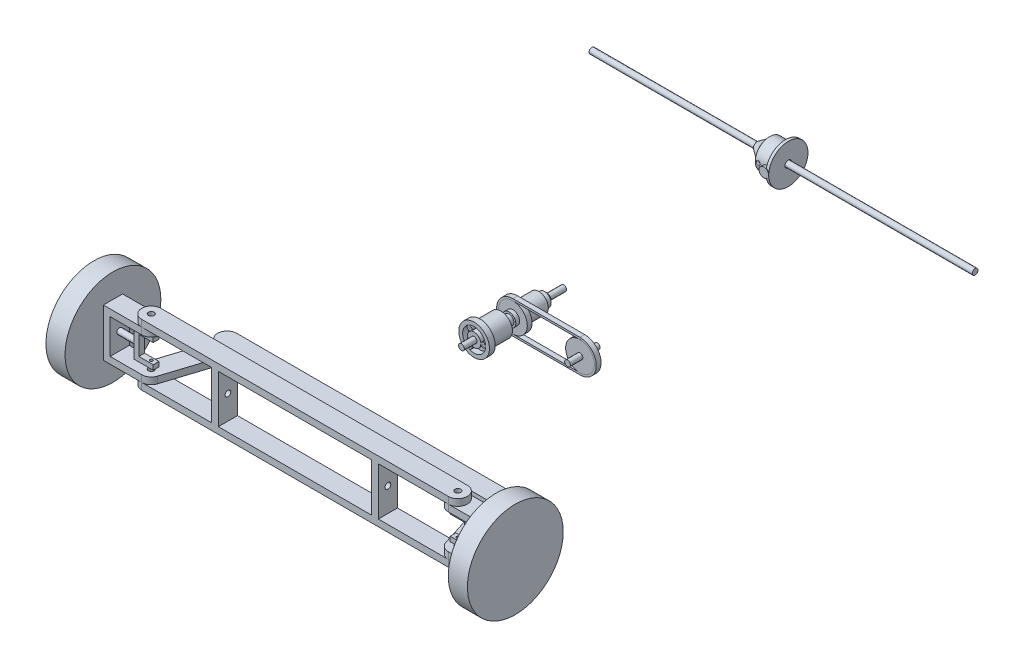
SolidWorks part; units mm, degrees
other "RD Pinion"
other "RD Ring Gear"
other "RD L Gear Right"
other "RD L Gear Left"
other "RD S Gear Outer"
other "RD S Gear Inner"
other "RD S Gear Inner"
other "Tie Plate"
other "Front Right Knuckle"
other "Front Left Knuckle"
other "Front Plate"
other "Main Shaft"
other "Front Right Wheel"
other "Front Left Wheel"
ref_plane "Front Plane" through (0, 0, 0) normal (0, 0, 1) x (1, 0, 0)
ref_plane "Top Plane" through (0, 0, 0) normal (0, 1, 0) x (1, 0, 0)
ref_plane "Right Plane" through (0, 0, 0) normal (1, 0, 0) x (0, 0, -1)
sketch "Top View Layout" plane through (0, 0, 0) normal (0, 1, 0) x (1, 0, 0)
  line L0 (-100, 125) -> (100, 125)
  line L1 (0, 125) -> (0, -125)
  line L2 (-100, -125) -> (100, -125)
  line L3 (0, -15) -> (35, -15) construction
  line L4 (35, -15) -> (35, -125) construction
  line L5 (2.5, 114.75) -> (2.5, 135.25) construction
  line L6 (-2.5, 114.75) -> (2.5, 114.75) construction
  line L7 (-8.75, 127) -> (-2.75, 127) construction
  line L8 (-2.5, 114.75) -> (2.5, 114.75) construction
  line L9 (-2.5, 114.75) -> (-2.5, 116.25) construction
  line L10 (-2.5, 116.25) -> (2.5, 116.25) construction
  line L11 (2.5, 114.75) -> (2.5, 116.25) construction
  line L12 (2.5, 135.25) -> (1, 135.25) construction
  line L13 (2.5, 135.25) -> (2.5, 114.75) construction
  line L14 (2.5, 114.75) -> (1, 114.75) construction
  line L15 (1, 135.25) -> (1, 114.75) construction
  line L16 (-4.25, 128.5) -> (-2.75, 128.5) construction
  line L17 (-4.25, 128.5) -> (-4.25, 121.5) construction
  line L18 (-4.25, 121.5) -> (-2.75, 121.5) construction
  line L19 (-2.75, 128.5) -> (-2.75, 121.5) construction
  line L20 (-4.25, 128.5) -> (-2.75, 121.5) construction
  line L21 (-4.25, 121.5) -> (-2.75, 128.5) construction
  line L22 (-8.75, 128.5) -> (-7.25, 128.5) construction
  line L23 (-8.75, 128.5) -> (-8.75, 121.5) construction
  line L24 (-8.75, 121.5) -> (-7.25, 121.5) construction
  line L25 (-7.25, 128.5) -> (-7.25, 121.5) construction
  line L26 (-8.75, 128.5) -> (-7.25, 121.5) construction
  line L27 (-8.75, 121.5) -> (-7.25, 128.5) construction
  line L28 (-8.75, 123) -> (-2.75, 123) construction
  line L29 (-5.75, 123) -> (-5.75, 120.2863) construction
  line L30 (-5.75, 127) -> (-5.75, 129.2691) construction
  point P8 (0, 114.75)
  point P9 (0, 0)
  point P11 (2.5, 125)
  point P16 (2.5, 125)
  point P19 (0, 114.75)
  point P23 (-3.5, 125)
  point P28 (-8, 125)
  dimension "D1" = 250
  dimension "D2" = 200
  dimension "D3" = 35
  dimension "D4" = 15
  dimension "D5" = 5
  dimension "D6" = 20.5
  dimension "D7" = 1.5
  dimension "D8" = 1.5
  dimension "D9" = 1.5
  dimension "D10" = 7
  dimension "D11" = 3.5
  dimension "D12" = 8
  dimension "D13" = 1.5
  dimension "D14" = 1.5
ref_plane "Left" through (100, 0, 0) normal (-1, 0, 0) x (0, 0, 1)
ref_plane "Right" through (-100, 0, 0) normal (-1, 0, 0) x (0, 0, 1)
sketch "Left Wheels" plane through (100, 0, 0) normal (-1, 0, 0) x (0, 0, 1)
  circle A0 centre (125, 0) radius 25
  circle A1 centre (-125, 0) radius 25
  dimension "D1" = 50
  dimension "D2" = 50
sketch "Right Wheels" plane through (-100, 0, 0) normal (-1, 0, 0) x (0, 0, 1)
  circle A0 centre (-125, 0) radius 25 construction
  circle A1 centre (125, 0) radius 25 construction
  circle A2 centre (-125, 0) radius 25
  circle A3 centre (125, 0) radius 25
ref_plane "Rear Differential Pinion Plane" through (0, 0, -114.75) normal (0, 0, 1) x (1, 0, 0)
sketch "Rear Differential Pinion Profile" plane through (0, 0, -114.75) normal (0, 0, 1) x (1, 0, 0)
  circle A0 centre (0, 0) radius 2.5
ref_plane "Rear Differential Ring Gear Plane" through (2.5, 0, 0) normal (1, 0, 0) x (0, 0, -1)
ref_plane "Rear Axle" through (0, 0, -125) normal (0, 0, 1) x (1, 0, 0)
sketch "Rear Differential Ring Gear Profile" plane through (2.5, 0, 0) normal (1, 0, 0) x (0, 0, -1)
  line L0 (114.75, 0) -> (135.25, 0) construction
  circle A0 centre (125, 0) radius 10.25
extrude "Rear Differential Pinion" add sketch "Rear Differential Pinion Profile" against normal blind 1.5 contours A0
extrude "Rear Differential Ring Gear" add sketch "Rear Differential Ring Gear Profile" against normal blind 1.5 separate body contours A0
ref_plane "RD Inner L Gear Plane" through (-2.75, 0, 0) normal (1, 0, 0) x (0, 0, -1)
ref_plane "RD Outer L Gear Plane" through (-8.75, 0, 0) normal (1, 0, 0) x (0, 0, -1)
sketch "RD Inner L Gear Profile" plane through (-2.75, 0, 0) normal (1, 0, 0) x (0, 0, -1)
  circle A0 centre (125, 0) radius 3.5
sketch "RD Outer L Gear Profile" plane through (-8.75, 0, 0) normal (1, 0, 0) x (0, 0, -1)
  line L0 (128.5, 0) -> (121.5, 0) construction
  circle A0 centre (125, 0) radius 3.5
ref_plane "RD Inner S Gear Plane" through (0, 0, -121.5) normal (0, 0, 1) x (1, 0, 0)
ref_plane "RD Outer S Gear Plane" through (0, 0, -128.5) normal (0, 0, 1) x (1, 0, 0)
sketch "RD Inner S Gear Profile" plane through (0, 0, -121.5) normal (0, 0, 1) x (1, 0, 0)
  line L0 (-8.75, 0) -> (-7.25, 0) construction
  circle A0 centre (-5.75, 0) radius 3
sketch "RD Outer S Gear Profile" plane through (0, 0, -128.5) normal (0, 0, 1) x (1, 0, 0)
  line L0 (-8.75, 0) -> (-7.25, 0) construction
  circle A2 centre (-5.75, 0) radius 3
extrude "RD Outer L Gear Extrude" add sketch "RD Outer L Gear Profile" along normal blind 1.5 separate body contours A0
extrude "RD Inner L Gear Extrude" add sketch "RD Inner L Gear Profile" against normal blind 1.5 separate body contours A0
extrude "RD Outer S Gear Extrude" add sketch "RD Outer S Gear Profile" along normal blind 1.5 separate body contours A2
extrude "RD Inner S Gear Extrude" add sketch "RD Inner S Gear Profile" against normal blind 1.5 separate body contours A0
sketch "RD Ring Gear Case Profile" plane through (1, 0, 0) normal (-1, 0, 0) x (0, 0, 1)
  line L0 (-121.5, 3.2113) -> (-121.5, -3.2113)
  line L1 (-128.5, 3.2113) -> (-128.5, -3.2113)
  line L2 (-121.5, 6.6332) -> (-121.5, 3.2113) construction
  line L3 (-128.5, 6.6332) -> (-128.5, 3.2113) construction
  line L4 (-121.5, -3.2113) -> (-121.5, -6.6332) construction
  line L5 (-128.5, -3.2113) -> (-128.5, -6.6332) construction
  circle A0 centre (-125, 0) radius 7.5
  arc A1 (-121.5, 3.2113) -> (-128.5, 3.2113) centre (-125, 0) ccw
  arc A2 (-121.5, -3.2113) -> (-121.5, 3.2113) centre (-125, 0) ccw construction
  arc A3 (-128.5, 3.2113) -> (-128.5, -3.2113) centre (-125, 0) ccw construction
  arc A4 (-128.5, -3.2113) -> (-121.5, -3.2113) centre (-125, 0) ccw
  point P7 (-121.5, 0)
  dimension "D1" = 15
  dimension "D2" = 9.5
extrude "RD Ring Gear Case " add sketch "RD Ring Gear Case Profile" along normal blind 8.25
sketch "Sketch11" plane through (-7.25, 0, 0) normal (-1, 0, 0) x (0, 0, 1)
  circle A0 centre (-125, 0) radius 5.5
  circle A1 centre (-125, 0) radius 4.75
  arc A2 (-121.5, 3.2113) -> (-128.5, 3.2113) centre (-125, 0) ccw construction
  dimension "D1" = 11
extrude "Boss-Extrude8" add sketch "Sketch11" along normal up to vertex up to point (-8.75, 0, -128.5)
fillet "Fillet1" radius 2 1 edges at (-7.25, 0, -119.5)
sketch "Sketch12" plane through (0, 0, -125) normal (0, 0, 1) x (1, 0, 0)
  line L0 (-8.75, 0) -> (-13.75, 0) construction
  line L1 (-8.75, 0) -> (-7.25, 0) construction
  line L2 (-8.75, 0) -> (-7.25, 0) construction
  line L3 (-100, 0) -> (100, 0) construction
  line L4 (-100, 0) -> (100, 0) construction
  line L5 (-8.75, 5.5) -> (-8.75, -5.5) construction
  line L6 (-13.75, 0) -> (-13.75, 2)
  line L7 (-13.75, 2) -> (-8.75, 5.5)
  line L8 (-13.75, 0) -> (-8.75, 0)
  line L9 (-8.75, 0) -> (-8.75, 5.5)
  point P15 (-13.75, 1)
  dimension "D1" = 5
  dimension "D2" = 2
revolve "Revolve1" add sketch "Sketch12" angle 360 about L0
sketch "Sketch13" plane through (2.5, 0, 0) normal (1, 0, 0) x (0, 0, -1)
  circle A0 centre (125, 0) radius 1.75
  dimension "D1" = 3.5
extrude "Cut-Extrude1" cut sketch "Sketch13" against normal through all
sketch "Sketch14" plane through (0, 0, -121.5) normal (0, 0, 1) x (1, 0, 0)
  circle A0 centre (-5.75, 0) radius 1
  dimension "D1" = 2
extrude "Boss-Extrude9" add sketch "Sketch14" along normal blind 4
sketch "Sketch15" plane through (0, 0, -121.5) normal (0, 0, 1) x (1, 0, 0)
  circle A0 centre (-5.75, 0) radius 1.1
  dimension "D1" = 2.2
extrude "Cut-Extrude2" cut sketch "Sketch15" against normal through all both and the other way through all
extrude "Boss-Extrude10" add sketch "Sketch14<2>" against normal blind 4 from surface starting at face at (-2.75, 0, -128.5)
sketch "Sketch14<2>" plane through (0, 0, -121.5) normal (0, 0, 1) x (1, 0, 0) same geometry as "Sketch14"
sketch "Sketch16" plane through (-8.75, 0, 0) normal (-1, 0, 0) x (0, 0, 1)
  circle A0 centre (-125, 0) radius 1.5
  dimension "D1" = 3
extrude "Boss-Extrude11" add sketch "Sketch16" along normal up to vertex (91.25 mm away) up to point (-100, 0, -125)
sketch "Sketch17" plane through (-2.75, 0, 0) normal (1, 0, 0) x (0, 0, -1)
  circle A0 centre (125, 0) radius 1.5 construction
  circle A1 centre (125, 0) radius 1.5
extrude "Boss-Extrude12" add sketch "Sketch17" along normal up to vertex (102.75 mm away) up to point (100, 0, -125)
sketch "Transfer Case Layout" plane through (0, 0, 0) normal (0, 1, 0) x (1, 0, 0)
  line L0 (0, 125) -> (0, -125) construction
  line L1 (-7.5, -13.75) -> (7.5, -13.75)
  line L2 (-7.5, -13.75) -> (-7.5, -16.25)
  line L3 (-7.5, -16.25) -> (7.5, -16.25)
  line L4 (7.5, -13.75) -> (7.5, -16.25)
  line L5 (-7.5, -13.75) -> (7.5, -16.25) construction
  line L6 (-7.5, -16.25) -> (7.5, -13.75) construction
  line L7 (27.5, -13.75) -> (42.5, -13.75)
  line L8 (27.5, -13.75) -> (27.5, -16.25)
  line L9 (27.5, -16.25) -> (42.5, -16.25)
  line L10 (42.5, -13.75) -> (42.5, -16.25)
  line L11 (27.5, -13.75) -> (42.5, -16.25) construction
  line L12 (27.5, -16.25) -> (42.5, -13.75) construction
  line L13 (2.5, -17.25) -> (-2.5, -17.25)
  line L14 (2.5, -17.25) -> (2.5, -16.25)
  line L15 (2.5, -16.25) -> (-2.5, -16.25)
  line L16 (-2.5, -17.25) -> (-2.5, -16.25)
  line L17 (2.5, -17.25) -> (-2.5, -16.25) construction
  line L18 (2.5, -16.25) -> (-2.5, -17.25) construction
  line L19 (-2, -4.75) -> (-2, -10.75)
  line L20 (3.5, -18.25) -> (-3.5, -18.25)
  line L21 (3.5, -18.25) -> (3.5, -16.25)
  line L22 (3.5, -16.25) -> (-3.5, -16.25)
  line L23 (-3.5, -18.25) -> (-3.5, -16.25)
  line L24 (3.5, -18.25) -> (-3.5, -16.25) construction
  line L25 (3.5, -16.25) -> (-3.5, -18.25) construction
  line L26 (2.5, -20) -> (-2.5, -20)
  line L27 (2.5, -20) -> (2.5, -17.5)
  line L28 (2.5, -17.5) -> (-2.5, -17.5)
  line L29 (-2.5, -20) -> (-2.5, -17.5)
  line L30 (2.5, -20) -> (-2.5, -17.5) construction
  line L31 (2.5, -17.5) -> (-2.5, -20) construction
  line L32 (-3.5, -9.25) -> (3.5, -9.25)
  line L33 (-3.5, -9.25) -> (-3.5, -10.75)
  line L34 (-3.5, -10.75) -> (3.5, -10.75)
  line L35 (3.5, -9.25) -> (3.5, -10.75)
  line L36 (-3.5, -9.25) -> (3.5, -10.75) construction
  line L37 (-3.5, -10.75) -> (3.5, -9.25) construction
  line L38 (-3.5, -4.75) -> (3.5, -4.75)
  line L39 (-3.5, -4.75) -> (-3.5, -6.25)
  line L40 (-3.5, -6.25) -> (3.5, -6.25)
  line L41 (3.5, -4.75) -> (3.5, -6.25)
  line L42 (-3.5, -4.75) -> (3.5, -6.25) construction
  line L43 (-3.5, -6.25) -> (3.5, -4.75) construction
  line L44 (2, -4.75) -> (2, -10.75)
  line L45 (0, -6.25) -> (0, -9.25) construction
  line L46 (-5, -2.75) -> (5, -2.75) construction
  line L47 (-5, -2.75) -> (-5, -12.75) construction
  line L48 (-5, -12.75) -> (5, -12.75) construction
  line L49 (5, -2.75) -> (5, -12.75) construction
  line L50 (-5, -2.75) -> (5, -12.75) construction
  line L51 (-5, -12.75) -> (5, -2.75) construction
  line L52 (-6, -22.5) -> (-6, -24)
  line L53 (-2.5, -1.75) -> (2.5, -1.75)
  line L54 (-2.5, -1.75) -> (-2.5, -2.75)
  line L55 (-2.5, -2.75) -> (2.5, -2.75)
  line L56 (2.5, -1.75) -> (2.5, -2.75)
  line L57 (-2.5, -1.75) -> (2.5, -2.75) construction
  line L58 (-2.5, -2.75) -> (2.5, -1.75) construction
  line L59 (-2.5, 1.25) -> (2.5, 1.25)
  line L60 (-2.5, 1.25) -> (-2.5, -0.75)
  line L61 (-2.5, -0.75) -> (2.5, -0.75)
  line L62 (2.5, 1.25) -> (2.5, -0.75)
  line L63 (-2.5, 1.25) -> (2.5, -0.75) construction
  line L64 (-2.5, -0.75) -> (2.5, 1.25) construction
  line L65 (3.5, 0.25) -> (-3.5, 0.25)
  line L66 (3.5, 0.25) -> (3.5, -2.25)
  line L67 (3.5, -2.25) -> (-3.5, -2.25)
  line L68 (-3.5, 0.25) -> (-3.5, -2.25)
  line L69 (3.5, 0.25) -> (-3.5, -2.25) construction
  line L70 (3.5, -2.25) -> (-3.5, 0.25) construction
  line L71 (-2.5, -22.5) -> (2.5, -22.5)
  line L72 (-2.5, -22.5) -> (-2.5, -27.5)
  line L73 (-2.5, -27.5) -> (2.5, -27.5)
  line L74 (2.5, -22.5) -> (2.5, -27.5)
  line L75 (-2.5, -22.5) -> (2.5, -27.5) construction
  line L76 (-2.5, -27.5) -> (2.5, -22.5) construction
  line L77 (-6, -24) -> (6, -24)
  line L78 (6, -24) -> (6, -22.5)
  line L79 (6, -22.5) -> (-6, -22.5)
  line L80 (-4.5, -22.5) -> (-4.5, -24)
  line L81 (4.5, -22.5) -> (4.5, -24)
  line L82 (-6, -24) -> (-6, -33.5) construction
  line L83 (2.5, -29.5) -> (-2.5, -29.5)
  line L84 (2.5, -29.5) -> (2.5, -28)
  line L85 (2.5, -28) -> (-2.5, -28)
  line L86 (-2.5, -29.5) -> (-2.5, -28)
  line L87 (2.5, -29.5) -> (-2.5, -28) construction
  line L88 (2.5, -28) -> (-2.5, -29.5) construction
  line L89 (-4.5, -26.5) -> (4.5, -26.5)
  line L90 (-4.5, -26.5) -> (-4.5, -29.5)
  line L91 (-4.5, -29.5) -> (4.5, -29.5)
  line L92 (4.5, -26.5) -> (4.5, -29.5)
  line L93 (-4.5, -26.5) -> (4.5, -29.5) construction
  line L94 (-4.5, -29.5) -> (4.5, -26.5) construction
  line L95 (6, -24) -> (6, -33.5) construction
  line L96 (-3.5, -33.5) -> (-3.5, -36.5)
  line L97 (6, -36.5) -> (-6, -36.5)
  line L98 (6, -36.5) -> (6, -33.5)
  line L99 (6, -33.5) -> (-6, -33.5)
  line L100 (-6, -36.5) -> (-6, -33.5)
  line L101 (6, -36.5) -> (-6, -33.5) construction
  line L102 (6, -33.5) -> (-6, -36.5) construction
  line L103 (3.5, -33.5) -> (3.5, -36.5)
  line L104 (0, -28) -> (0, -43.1129)
  line L109 (8, -36.5) -> (-8, -36.5)
  line L110 (8, -36.5) -> (8, -33.5)
  line L111 (8, -33.5) -> (-8, -33.5)
  line L112 (-8, -36.5) -> (-8, -33.5)
  line L113 (8, -36.5) -> (-8, -33.5) construction
  line L114 (8, -33.5) -> (-8, -36.5) construction
  line L115 (0, -27.5) -> (0, -9.25)
  line L116 (0, -6.25) -> (0, -1.75)
  line L117 (0, -0.75) -> (0, 11.0375)
  line L118 (35, -22.7597) -> (35, -7.2403)
  point P0 (0, -15)
  point P6 (35, -15)
  point P12 (0, -16.75)
  point P19 (0, -17.25)
  point P24 (0, -18.75)
  point P29 (0, -10)
  point P34 (0, -5.5)
  point P43 (0, -7.75)
  point P50 (0, -2.25)
  point P55 (0, 0.25)
  point P60 (0, -1)
  point P65 (0, -25)
  point P72 (0, -22.5)
  point P79 (0, -28.75)
  point P84 (0, -28)
  point P92 (0, -35)
  point P98 (0, -35)
  point P99 (0, -35)
  point P113 (35, -15)
  dimension "D1" = 2.5
  dimension "D2" = 2.5
  dimension "D3" = 15
  dimension "D4" = 15
  dimension "D5" = 1
  dimension "D6" = 5
  dimension "D7" = 7
  dimension "D8" = 2
  dimension "D9" = 0.25
  dimension "D10" = 2.5
  dimension "D11" = 7
  dimension "D12" = 5
  dimension "D13" = 1.5
  dimension "D14" = 1.5
  dimension "D15" = 1.5
  dimension "D16" = 1.5
  dimension "D17" = 6
  dimension "D18" = 2
  dimension "D19" = 1.5
  dimension "D20" = 5
  dimension "D21" = 1
  dimension "D22" = 2
  dimension "D23" = 1
  dimension "D24" = 7
  dimension "D25" = 2.5
  dimension "D26" = 0.5
  dimension "D27" = 5
  dimension "D28" = 5
  dimension "D29" = 10
  dimension "D30" = 1.5
  dimension "D31" = 12
  dimension "D32" = 1.5
  dimension "D33" = 1.5
  dimension "D34" = 1.5
  dimension "D35" = 0.5
  dimension "D36" = 3
  dimension "D37" = 3
  dimension "D38" = 20
  dimension "D39" = 2.5
  dimension "D40" = 2.5
  dimension "D41" = 7
  dimension "D42" = 2
  dimension "D43" = 16
ref_plane "FWD Sprocket Plane" through (0, 0, 15) normal (0, 0, 1) x (1, 0, 0)
sketch "Sketch19" plane through (0, 0, 15) normal (0, 0, 1) x (1, 0, 0)
  circle A0 centre (35, 0) radius 7.5
  circle A1 centre (0, 0) radius 7.5
  point P6 (7.5, 0)
  point P9 (27.5, 0)
extrude "FWD Sprockets" add sketch "Sketch19" along normal up to vertex (1.25 mm away) and the other way up to vertex (1.25 mm away) separate body up to point (-7.5, 0, 16.25) other way up to point (-7.5, 0, 13.75)
sketch "Sketch20" plane through (0, 0, 15) normal (0, 0, 1) x (1, 0, 0)
  line L0 (0, 8.5) -> (35, 8.5)
  line L1 (0, -8.5) -> (35, -8.5)
  line L2 (0, 7.5) -> (35, 7.5)
  line L3 (0, -7.5) -> (35, -7.5)
  circle A0 centre (0, 0) radius 7.5 construction
  arc A1 (0, 7.5) -> (0, -7.5) centre (0, 0) ccw
  circle A2 centre (35, 0) radius 7.5 construction
  arc A3 (35, -7.5) -> (35, 7.5) centre (35, 0) ccw
  arc A4 (0, 8.5) -> (0, -8.5) centre (0, 0) ccw
  arc A5 (35, -8.5) -> (35, 8.5) centre (35, 0) ccw
  arc A6 (4, -7.5) -> (4, 7.5) centre (0, 0) ccw construction
  arc A7 (0, -7.5) -> (0, 7.5) centre (0, 0) ccw construction
  arc A8 (35, 7.5) -> (35, -7.5) centre (35, 0) ccw construction
  arc A9 (31, 7.5) -> (31, -7.5) centre (35, 0) ccw construction
  arc A10 (4, 7.5) -> (0, 8.5) centre (0, 0) ccw construction
  arc A11 (35, 8.5) -> (31, 7.5) centre (35, 0) ccw construction
  arc A12 (31, -7.5) -> (35, -8.5) centre (35, 0) ccw construction
  arc A13 (0, -8.5) -> (4, -7.5) centre (0, 0) ccw construction
  dimension "D1" = 1
  dimension "D2" = 1
extrude "FWD Sprocket Chain" add sketch "Sketch20" along normal up to surface and the other way up to surface separate body up to face at (7.5, 0, 16.25) other way up to face at (7.5, 0, 13.75)
sketch "Sketch21" plane through (0, 0, 16.25) normal (0, 0, 1) x (1, 0, 0)
  circle A0 centre (0, 0) radius 2.5
  point P3 (2.5, 0)
extrude "FWD Sprocket Dog Gear" add sketch "Sketch21" along normal up to vertex (1 mm away) up to point (-2.5, 0, 17.25)
ref_plane "Mode Sleeve Gear Plane" through (0, 0, 18.25) normal (0, 0, 1) x (1, 0, 0)
sketch "Sketch22" plane through (0, 0, 18.25) normal (0, 0, 1) x (1, 0, 0)
  circle A0 centre (0, 0) radius 3.5
  circle A1 centre (0, 0) radius 2.5 construction
  circle A2 centre (0, 0) radius 2.5
extrude "Mode Sleeve Gear" add sketch "Sketch22" against normal up to vertex (2 mm away) separate body up to point (3.5, 0, 16.25)
sketch "Sketch23" plane through (0, 0, 18.25) normal (0, 0, 1) x (1, 0, 0)
  circle A0 centre (0, 0) radius 2.5 construction
  circle A1 centre (0, 0) radius 2.5
extrude "Mode Sleeve Main Shaft Gear" add sketch "Sketch23" along normal up to vertex (1.75 mm away) and the other way up to vertex (0.75 mm away) separate body up to point (2.5, 0, 20) other way up to point (2.5, 0, 17.5)
ref_plane "Range Sleeve Rear Plane" through (0, 0, 22.5) normal (0, 0, 1) x (1, 0, 0)
sketch "Sketch24" plane through (0, 0, 22.5) normal (0, 0, 1) x (1, 0, 0)
  circle A0 centre (0, 0) radius 2.5
extrude "Main Shaft Range Sleeve Gear" add sketch "Sketch24" along normal up to vertex (5 mm away) separate body up to point (-2.5, 0, 27.5)
sketch "Sketch25" plane through (0, 0, 22.5) normal (0, 0, 1) x (1, 0, 0)
  circle A0 centre (0, 0) radius 6
  circle A3 centre (0, 0) radius 4.5
extrude "Carrier Range Sleeve Gear" add sketch "Sketch25" along normal up to vertex (1.5 mm away) separate body up to point (6, 0, 24)
ref_plane "Range Sleeve Input Shaft Side" through (0, 0, 29.5) normal (0, 0, 1) x (1, 0, 0)
sketch "Sketch27" plane through (0, 0, 29.5) normal (0, 0, 1) x (1, 0, 0)
  circle A0 centre (0, 0) radius 2.5
extrude "Input Range Sleeve Gear" add sketch "Sketch27" against normal up to vertex (1.5 mm away) separate body up to point (2.5, 0, 28)
sketch "Sketch28" plane through (0, 0, 29.5) normal (0, 0, 1) x (1, 0, 0)
  circle A0 centre (0, 0) radius 4.5
  circle A1 centre (0, 0) radius 2.5 construction
  circle A2 centre (0, 0) radius 2.5
extrude "Range Sleeve Sleeve Gear" add sketch "Sketch28" against normal up to vertex (3 mm away) separate body up to point (4.5, 0, 26.5)
ref_plane "Planetary Input Side Plane" through (0, 0, 36.5) normal (0, 0, 1) x (1, 0, 0)
sketch "Sketch29" plane through (0, 0, 36.5) normal (0, 0, 1) x (1, 0, 0)
  circle A0 centre (0, 0) radius 3.5
extrude "Planetary Sun Gear" add sketch "Sketch29" against normal up to vertex (3 mm away) separate body up to point (3.5, 0, 33.5)
sketch "Sketch30" plane through (0, 0, 36.5) normal (0, 0, 1) x (1, 0, 0)
  line L0 (6, 0) -> (-6, 0) construction
  circle A0 centre (4.75, 0) radius 1.25
extrude "Planetary Planet Gear" add sketch "Sketch30" against normal up to vertex (3 mm away) separate body up to point (6, 0, 33.5)
pattern_circular "Planetary Planet Gear x 3" count 3 over 360 about axis through (0, 0, 28) along (0, 0, 1) reverse direction yes of bodies 132
sketch "Sketch31" plane through (0, 0, 36.5) normal (0, 0, 1) x (1, 0, 0)
  circle A0 centre (0, 0) radius 6
  circle A1 centre (0, 0) radius 8
extrude "Planetary Ring Gear" add sketch "Sketch31" against normal up to vertex (3 mm away) separate body up to point (8, 0, 33.5)
ref_plane "Planetary Rear Side Plane" through (0, 0, 33.5) normal (0, 0, 1) x (1, 0, 0)
sketch "Sketch32" plane through (0, 0, 33.5) normal (0, 0, 1) x (1, 0, 0)
  line L0 (3.5, 0) -> (6, 0) construction
  line L1 (0, 0) -> (4.75, 0) construction
  line L2 (0, 0) -> (-2.375, -4.1136) construction
  circle A0 centre (0, 0) radius 6
  circle A1 centre (4.75, 0) radius 0.5
  circle A2 centre (-2.375, -4.1136) radius 0.5
  circle A3 centre (-2.375, 4.1136) radius 0.5
  point P4 (4.75, 0)
  dimension "D1" = 1
  dimension "D3" = 120
  dimension "D4" = 4.75
  dimension "D2" = 3
extrude "Carrier" add sketch "Sketch32" against normal blind 1 separate body contours A3 | A0 A3 A2 A1 | A1 | A2 region at (0, 0, 33.5) region at (4.75, 0, 33.5) region at (-2.375, -4.1136, 33.5) region at (-2.375, 4.1136, 33.5)
extrude "Carrier Shafts" add sketch "Sketch32<3>" along normal up to vertex (3 mm away) contours A1 | A2 | A3 region at (4.75, 0, 33.5) region at (-2.375, -4.1136, 33.5) up to point (-3.5, 0, 36.5)
sketch "Sketch32<3>" plane through (0, 0, 33.5) normal (0, 0, 1) x (1, 0, 0) same geometry as "Sketch32"
sketch "Sketch33" plane through (0, 0, 33.5) normal (0, 0, 1) x (1, 0, 0)
  circle A0 centre (0, 0) radius 6 construction
  circle A1 centre (0, 0) radius 6
  circle A2 centre (0, 0) radius 5.5
  dimension "D1" = 0.5
extrude "Carrier Range Sleeve Gear Connect" add sketch "Sketch33" against normal up to surface (9.5 mm away) up to face at (6, 0, 24)
ref_plane "Center Diff Main Shaft Sidegear Plane" through (0, 0, 10.75) normal (0, 0, 1) x (1, 0, 0)
sketch "Sketch34" plane through (0, 0, 10.75) normal (0, 0, 1) x (1, 0, 0)
  circle A0 centre (0, 0) radius 3.5
extrude "Center Diff Main Shaft Side Gear" add sketch "Sketch34" against normal up to vertex (1.5 mm away) separate body up to point (3.5, 0, 9.25)
ref_plane "Center Diff Rear Shaft Sidegear Plane" through (0, 0, 4.75) normal (0, 0, 1) x (1, 0, 0)
ref_plane "Center Diff Mid Plane" through (0, 0, 7.75) normal (0, 0, 1) x (1, 0, 0)
mirror "Center Diff Rear Shaft Side Gear" about plane through (0, 0, 7.75) normal (0, 0, 1) of bodies 139
ref_plane "Center Diff Right Pinion Inner Plane" through (-2, 0, 0) normal (-1, 0, 0) x (0, 0, 1)
sketch "Sketch35" plane through (-2, 0, 0) normal (-1, 0, 0) x (0, 0, 1)
  line L0 (4.75, 0) -> (10.75, 0) construction
  circle A0 centre (7.75, 0) radius 3
extrude "Center Diff Right Pinion" add sketch "Sketch35" along normal up to vertex (1.5 mm away) separate body up to point (-3.5, 0, 10.75)
ref_plane "Center Diff Left Side Pinion Inner Plane" through (2, 0, 0) normal (-1, 0, 0) x (0, 0, 1)
sketch "Sketch36" plane through (2, 0, 0) normal (-1, 0, 0) x (0, 0, 1)
  line L0 (4.75, 0) -> (10.75, 0) construction
  circle A0 centre (7.75, 0) radius 3
extrude "Center Diff Left Pinion" add sketch "Sketch36" against normal up to vertex (1.5 mm away) separate body up to point (3.5, 0, 4.75)
ref_plane "Center Diff Rear Shaft Side Plane" through (0, 0, 2.75) normal (0, 0, 1) x (1, 0, 0)
sketch "Sketch37" plane through (0, 0, 2.75) normal (0, 0, 1) x (1, 0, 0)
  circle A0 centre (0, 0) radius 5
extrude "Center Diff Rear Axle Side Plate" add sketch "Sketch37" along normal up to vertex (2 mm away) separate body up to point (3.5, 0, 4.75)
mirror "Center Diff Main Shaft Side Plate" about plane through (0, 0, 7.75) normal (0, 0, 1) of bodies 143
sketch "Sketch38" plane through (0, 0, 2.75) normal (0, 0, 1) x (1, 0, 0)
  line L0 (3.5, -2.8284) -> (3.5, 2.8284)
  line L1 (-3.4263, -2.9173) -> (-3.5, -2.8284)
  line L2 (-3.5, -2.8284) -> (-3.5, 2.8284)
  circle A0 centre (0, 0) radius 5 construction
  circle A1 centre (0, 0) radius 5
  arc A2 (3.5, 2.8284) -> (-3.5, 2.8284) centre (0, 0) ccw
  arc A3 (3.5, -2.8284) -> (3.5, 2.8284) centre (0, 0) ccw construction
  arc A4 (-3.5, 2.8284) -> (-3.5, -2.8284) centre (0, 0) ccw construction
  arc A5 (-3.5, -2.8284) -> (3.5, -2.8284) centre (0, 0) ccw
  dimension "D1" = 0.5
extrude "Center Diff Case" add sketch "Sketch38" along normal up to surface (8 mm away) contours A1 A5 L2 A2 L0 region at (-4.8586, 0, 2.75) up to face at (5, 0, 10.75)
sketch "Sketch39" plane through (0, 0, 2.75) normal (0, 0, 1) x (1, 0, 0)
  circle A0 centre (0, 0) radius 2.5
extrude "Center Diff Lock Gear" add sketch "Sketch39" against normal up to vertex (1 mm away) up to point (2.5, 0, 1.75)
ref_plane "Lock Sleeve Plane" through (0, 0, -0.25) normal (0, 0, 1) x (1, 0, 0)
sketch "Sketch41" plane through (0, 0, -0.25) normal (0, 0, 1) x (1, 0, 0)
  circle A0 centre (0, 0) radius 3.5
  circle A1 centre (0, 0) radius 2.5 construction
  circle A2 centre (0, 0) radius 2.5
extrude "Lock Sleeve" add sketch "Sketch41" along normal up to vertex (2.5 mm away) separate body up to point (-3.5, 0, 2.25)
sketch "Sketch42" plane through (0, 0, -0.25) normal (0, 0, 1) x (1, 0, 0)
  circle A0 centre (0, 0) radius 2.5 construction
  circle A1 centre (0, 0) radius 2.5
extrude "Lock Sleeve Rear Shaft Gear" add sketch "Sketch42" along normal up to vertex (1 mm away) and the other way up to vertex (1 mm away) separate body up to point (2.5, 0, 0.75) other way up to point (2.5, 0, -1.25)
sketch "Sketch43" plane through (-2, 0, 0) normal (-1, 0, 0) x (0, 0, 1)
  line L0 (4.75, 0) -> (10.75, 0) construction
  circle A0 centre (7.75, 0) radius 0.5
  dimension "D1" = 1
extrude "Center Diff Pinion Rotation Point Cut" cut sketch "Sketch43" against normal through all both and the other way through all
sketch "Sketch45" plane through (0, 0, 2.75) normal (0, 0, 1) x (1, 0, 0)
  circle A0 centre (0, 0) radius 0.5
  dimension "D1" = 1
extrude "Center Diff Side Gear Rotation Point" cut sketch "Sketch45" against normal through all both and the other way through all
sketch "Sketch46" plane through (0, 0, -0.25) normal (0, 0, 1) x (1, 0, 0)
  circle A0 centre (0, 0) radius 1.5
  dimension "D1" = 3
extrude "Rear Shaft" add sketch "Sketch46" along normal up to vertex (1 mm away) and the other way blind 10 up to point (0, 0, 0.75)
sketch "Sketch47" plane through (0, 0, 2.75) normal (0, 0, 1) x (1, 0, 0)
  circle A0 centre (0, 0) radius 0.5
  dimension "D1" = 1
extrude "Center Diff Rear Shaft Side Axle" add sketch "Sketch47" along normal up to vertex (3.5 mm away) and the other way up to vertex (1 mm away) up to point (0, 0, 6.25) other way up to point (0, 0, 1.75)
sketch "Sketch48" plane through (-2, 0, 0) normal (-1, 0, 0) x (0, 0, 1)
  circle A0 centre (7.75, 0) radius 0.5 construction
  circle A1 centre (7.75, 0) radius 0.5
extrude "Center Diff Right Side Pinion Axle" add sketch "Sketch48" along normal up to vertex (3 mm away) up to point (-5, 0, 12.75)
sketch "Sketch49" plane through (2, 0, 0) normal (-1, 0, 0) x (0, 0, 1)
  circle A0 centre (7.75, 0) radius 0.5 construction
  circle A1 centre (7.75, 0) radius 0.5
extrude "Center Diff Left Side Pinion Axle" add sketch "Sketch49" against normal up to vertex (3 mm away) up to point (5, 0, 2.75)
sketch "Sketch50" plane through (0, 0, 18.25) normal (0, 0, 1) x (1, 0, 0)
  circle A0 centre (0, 0) radius 0.5
  dimension "D1" = 1
extrude "Main Shaft Sprocket Rotation Point Cut" cut sketch "Sketch50" against normal through all both and the other way through all
extrude "Main Shaft Extrude" add sketch "Sketch50<2>" against normal up to vertex (9 mm away) and the other way up to vertex (9.25 mm away) up to point (0, 0, 9.25) other way up to point (0, 0, 27.5)
sketch "Sketch50<2>" plane through (0, 0, 18.25) normal (0, 0, 1) x (1, 0, 0) same geometry as "Sketch50"
sketch "Sketch52" plane through (0, 0, 36.5) normal (0, 0, 1) x (1, 0, 0)
  circle A0 centre (0, 0) radius 1.5
  dimension "D1" = 3
extrude "Input Shaft Carrier Cut" cut sketch "Sketch52" against normal through all both and the other way through all
extrude "Input Shaft" add sketch "Sketch52<2>" along normal up to vertex (6.6129 mm away) and the other way up to vertex (8.5 mm away) up to point (0, 0, 43.1129) other way up to point (0, 0, 28)
sketch "Sketch52<2>" plane through (0, 0, 36.5) normal (0, 0, 1) x (1, 0, 0) same geometry as "Sketch52"
sketch "Sketch54" plane through (0, 0, 15) normal (0, 0, 1) x (1, 0, 0)
  circle A0 centre (35, 0) radius 1.5
  dimension "D1" = 3
extrude "FW Shaft" add sketch "Sketch54" along normal up to vertex (7.7597 mm away) and the other way up to vertex (7.7597 mm away) up to point (35, 0, 22.7597) other way up to point (35, 0, 7.2403)
sketch "Steering Layout" plane through (0, 0, 0) normal (0, 1, 0) x (1, 0, 0)
  line L0 (0, 125) -> (80, -125) construction
  line L1 (-100, -125) -> (100, -125) construction
  line L2 (-80, -125) -> (0, 125) construction
  line L3 (-80, -125) -> (-70.4, -95)
  line L4 (-70.4, -95) -> (70.4, -95)
  line L5 (70.4, -95) -> (80, -125)
  dimension "D1" = 20
  dimension "D2" = 20
  dimension "D3" = 30
ref_plane "Y + 12.5mm" through (0, 12.5, 0) normal (0, 1, 0) x (1, 0, 0)
ref_plane "Y - 12.5mm" through (0, -12.5, 0) normal (0, 1, 0) x (1, 0, 0)
sketch "Front Plate Profile" plane through (0, 12.5, 0) normal (0, 1, 0) x (1, 0, 0)
  line L0 (-80, -120) -> (80, -120)
  line L1 (80, -130) -> (-80, -130)
  circle A0 centre (-80, -125) radius 1.5
  arc A1 (-80, -120) -> (-80, -130) centre (-80, -125) ccw
  circle A2 centre (80, -125) radius 1.5
  arc A3 (80, -130) -> (80, -120) centre (80, -125) ccw
  arc A4 (-80, -130) -> (-80, -120) centre (-80, -125) ccw construction
  arc A5 (80, -120) -> (80, -130) centre (80, -125) ccw construction
  dimension "D1" = 3
  dimension "D2" = 10
  dimension "D3" = 3
  dimension "D4" = 10
extrude "Upper Plate" add sketch "Front Plate Profile" along normal blind 3.5 separate body
mirror "Lower Plate" about plane through (0, 0, 0) normal (0, 1, 0) of bodies 164
sketch "Upper and Lower Plate Connect Profile" plane through (0, 12.5, 0) normal (0, 1, 0) x (1, 0, 0)
  line L0 (80, -120) -> (-80, -120) construction
  line L1 (40, -120) -> (43.5, -120)
  line L2 (40, -120) -> (40, -130)
  line L3 (40, -130) -> (43.5, -130)
  line L4 (43.5, -120) -> (43.5, -130)
  line L5 (-80, -130) -> (80, -130) construction
  line L6 (0, -120) -> (0, -130) construction
  line L7 (-43.5, -120) -> (-43.5, -130)
  line L8 (-40, -130) -> (-43.5, -130)
  line L9 (-40, -120) -> (-40, -130)
  line L10 (-40, -120) -> (-43.5, -120)
  dimension "D1" = 3.5
  dimension "D2" = 5
extrude "Upper and Lower Plate Connect" add sketch "Upper and Lower Plate Connect Profile" against normal up to surface (25 mm away) up to face at (0, -12.5, 125)
sketch "Front Axle Profile" plane through (0, 0, 0) normal (1, 0, 0) x (0, 0, -1)
  circle A0 centre (-125, 0) radius 1.5
  dimension "D1" = 3
extrude "Front Plate Front Axis Hole" cut sketch "Front Axle Profile" against normal through all both and the other way through all
sketch "Steering Knuckle Top Profile" plane through (0, 12.5, 0) normal (0, 1, 0) x (1, 0, 0)
  line L0 (80, -120) -> (100, -120)
  line L1 (100, -120) -> (100, -130)
  line L2 (100, -130) -> (80, -130)
  circle A0 centre (80, -125) radius 1.5 construction
  circle A1 centre (80, -125) radius 1.5
  arc A2 (80, -120) -> (80, -130) centre (80, -125) ccw
  arc A4 (80, -130) -> (80, -120) centre (80, -125) ccw construction
  dimension "D1" = 10
extrude "Top Steering Knuckle" add sketch "Steering Knuckle Top Profile" against normal blind 3.5 separate body
mirror "Bottom Steering Knuckle" about plane through (0, 0, 0) normal (0, 1, 0) of bodies 168
sketch "Steering Knuckle Side Profile" plane through (0, -9, 0) normal (0, 1, 0) x (1, 0, 0)
  line L0 (80, -130) -> (100, -130) construction
  line L1 (100, -120) -> (96.5, -120)
  line L2 (100, -120) -> (100, -130)
  line L3 (100, -130) -> (96.5, -130)
  line L4 (96.5, -120) -> (96.5, -130)
  dimension "D1" = 3.5
extrude "Steering Knuckle Side" add sketch "Steering Knuckle Side Profile" along normal up to surface (18 mm away) up to face at (80, 9, 126.5)
sketch "Steering Knuckle Shaft Profile" plane through (100, 0, 0) normal (1, 0, 0) x (0, 0, -1)
  circle A0 centre (-125, 0) radius 1.5
  dimension "D1" = 3
extrude "Steering Knuckle Shaft Cut" cut sketch "Steering Knuckle Shaft Profile" against normal through all both and the other way through all
sketch "Steering Knuckle Four Bar Profile" plane through (0, -9, 0) normal (0, 1, 0) x (1, 0, 0)
  line L0 (65.6379, -96.5239) -> (75.2379, -126.5239)
  line L1 (75.1621, -93.4761) -> (84.7621, -123.4761)
  arc A0 (75.1621, -93.4761) -> (65.6379, -96.5239) centre (70.4, -95) ccw
  circle A1 centre (70.4, -95) radius 1.5
  arc A2 (80, -120) -> (80, -130) centre (80, -125) ccw construction
  arc A3 (75.2379, -126.5239) -> (84.7621, -123.4761) centre (80, -125) ccw
  circle A4 centre (80, -125) radius 1.5 construction
  circle A5 centre (80, -125) radius 1.5
  arc A6 (65.6379, -96.5239) -> (75.1621, -93.4761) centre (70.4, -95) ccw construction
  arc A7 (84.7621, -123.4761) -> (75.2379, -126.5239) centre (80, -125) ccw construction
  dimension "D1" = 10
  dimension "D2" = 3
extrude "Steering Knuckle Four Bar" add sketch "Steering Knuckle Four Bar Profile" against normal up to surface (3.5 mm away) up to face at (80, -12.5, 126.5)
mirror "Steering Knuckle Mirror" about plane through (0, 0, 0) normal (1, 0, 0) of bodies 173 171
sketch "Tie Plate Profile" plane through (0, -9, 0) normal (0, 1, 0) x (1, 0, 0)
  line L0 (-70.4, -100) -> (70.4, -100)
  line L1 (-70.4, -90) -> (70.4, -90)
  arc A0 (70.4, -100) -> (70.4, -90) centre (70.4, -95) ccw
  arc A1 (75.1621, -93.4761) -> (65.6379, -96.5239) centre (70.4, -95) ccw construction
  arc A2 (-70.4, -90) -> (-70.4, -100) centre (-70.4, -95) ccw
  arc A3 (-65.6379, -96.5239) -> (-75.1621, -93.4761) centre (-70.4, -95) ccw construction
  circle A4 centre (70.4, -95) radius 1.5 construction
  circle A5 centre (-70.4, -95) radius 1.5 construction
  circle A6 centre (70.4, -95) radius 1.5
  circle A7 centre (-70.4, -95) radius 1.5
  arc A8 (-70.4, -100) -> (-70.4, -90) centre (-70.4, -95) ccw construction
  arc A9 (70.4, -90) -> (70.4, -100) centre (70.4, -95) ccw construction
  arc M8 (75.1621, -93.4761) -> (65.6379, -96.5239) centre (70.4, -95) ccw
  line M9 (65.6379, -96.5239) -> (75.2379, -126.5239)
  circle M14 centre (70.4, -95) radius 1.5
extrude "Tie Plate Extrude" add sketch "Tie Plate Profile" along normal blind 3.5 separate body contours A7 | M14 | L1 A2 L0 A7 M9 M8 | L0 A0 M8 M9 M14 region at (-3.7176, -9, 94.9924) region at (66.3288, -9, 98.2188) region at (70.4, -9, 95) region at (-70.4, -9, 95)
extrude "Tie Plate Attachment Bits" add sketch "Sketch63<3>" against normal blind 3.5 contours A7 | A6 region at (-70.4, -9, 95)
sketch "Sketch63<3>" plane through (0, -9, 0) normal (0, 1, 0) x (1, 0, 0) same geometry as "Tie Plate Profile"
ref_plane "L Wheel" through (100, 0, 0) normal (1, 0, 0) x (0, 0, -1)
sketch "Front Wheel Profile" plane through (100, 0, 0) normal (1, 0, 0) x (0, 0, -1)
  circle A0 centre (-125, 0) radius 25 construction
  circle A1 centre (-125, 0) radius 25
  circle A2 centre (-125, 0) radius 1.5 construction
  circle A3 centre (-125, 0) radius 1.5
extrude "Front Wheel" add sketch "Front Wheel Profile" along normal blind 10 separate body contours A3 | A1 A3 region at (100, 0, 149.2929) region at (100, 0, 125)
sketch "Front Wheel Shaft Profile" plane through (100, 0, 0) normal (1, 0, 0) x (0, 0, -1)
  circle A0 centre (-125, 0) radius 1.5 construction
  circle A1 centre (-125, 0) radius 1.5
extrude "Front Wheel Shaft" add sketch "Front Wheel Shaft Profile" against normal blind 15
ref_plane "Front Axle" through (0, 0, 125) normal (0, 0, 1) x (1, 0, 0)
sketch "Wheel U Joint Profile" plane through (0, 0, 125) normal (0, 0, 1) x (1, 0, 0)
  line L0 (85, 1.5) -> (85, -1.5) construction
  line L1 (85, 1.5) -> (85, -1.5)
  line L2 (-100, 0) -> (100, 0) construction
  line L3 (85, 7.5) -> (87.5, 7.5)
  line L4 (85, 5) -> (85, -5)
  line L5 (85, -7.5) -> (87.5, -7.5)
  line L6 (87.5, 7.5) -> (87.5, -7.5)
  line L7 (-100, 0) -> (100, 0) construction
  line L8 (87.5, 0) -> (63.8298, 0) construction
  line L9 (87.5, 7.5) -> (77.5, 7.5)
  line L10 (87.5, 7.5) -> (87.5, 5)
  line L11 (85, 5) -> (77.5, 5)
  line L12 (77.5, 7.5) -> (77.5, 5)
  line L13 (85, -5) -> (77.5, -5)
  line L14 (77.5, -7.5) -> (77.5, -5)
  line L15 (87.5, -7.5) -> (77.5, -7.5)
  line L16 (85, 7.5) -> (85, 5) construction
  line L17 (87.5, 5) -> (85, 5) construction
  line L18 (85, -5) -> (85, -7.5) construction
  line L19 (87.5, -5) -> (85, -5) construction
  dimension "D1" = 2.5
  dimension "D2" = 7.5
  dimension "D3" = 7.5
  dimension "D4" = 2.5
  dimension "D5" = 10
extrude "Wheel U Joint" add sketch "Wheel U Joint Profile" along normal blind 1.5 and the other way blind 1.5 contours L15 L5 L6 L3 L9 L12 L11 L4 L1 L13 L14 region at (85.1803, 3.25, 125)
sketch "Wheel U Joint Shaft Holes Profile" plane through (0, 7.5, 0) normal (0, 1, 0) x (1, 0, 0)
  circle A1 centre (80, -125) radius 0.75
  dimension "D1" = 1.5
extrude "Wheel U Joint Shaft Holes" cut sketch "Wheel U Joint Shaft Holes Profile" against normal through all both and the other way through all
mirror "Wheel Mirror" about plane through (0, 0, 0) normal (1, 0, 0) of bodies 179
